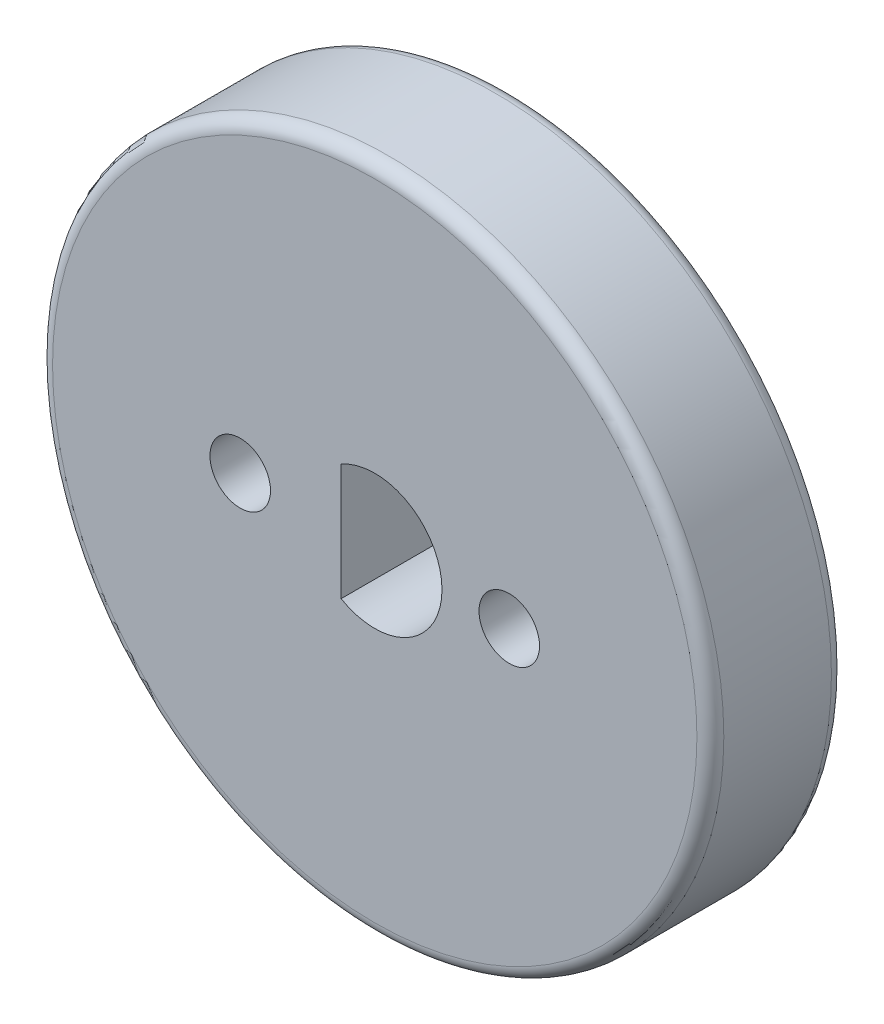
SolidWorks part; units mm, degrees
ref_plane "Front Plane" through (0, 0, 0) normal (0, 0, 1) x (1, 0, 0)
ref_plane "Top Plane" through (0, 0, 0) normal (0, 1, 0) x (1, 0, 0)
ref_plane "Right Plane" through (0, 0, 0) normal (1, 0, 0) x (0, 0, -1)
sketch "Sketch1" plane through (0, 0, 0) normal (0, 0, 1) x (1, 0, 0)
  line L0 (0, 0) -> (-2.5, -4.3301) construction
  line L1 (-2.5, -4.3301) -> (-2.5, 4.3301)
  line L2 (-2.5, 4.3301) -> (0, 0) construction
  line L3 (-5, 0) -> (0, 0) construction
  circle A0 centre (0, 0) radius 24.95
  circle A1 centre (0, 0) radius 15 construction
  circle A2 centre (0, 15) radius 2.25
  circle A3 centre (12.9904, -7.5) radius 2.25
  circle A4 centre (-12.9904, -7.5) radius 2.25
  arc A5 (-2.5, -4.3301) -> (-2.5, 4.3301) centre (0, 0) ccw
  point P13 (0, 0)
  dimension "D1" = 49.9
  dimension "D2" = 30
  dimension "D3" = 4.5
  dimension "D5" = 10
  dimension "D6" = 60
  dimension "D4" = 3
extrude "Boss-Extrude1" add sketch "Sketch1" along normal blind 6
sketch "Sketch2" plane through (0, 0, 6) normal (0, 0, 1) x (1, 0, 0)
  circle A0 centre (0, 0) radius 24.95
extrude "Boss-Extrude2" add sketch "Sketch2" along normal blind 4
sketch "Sketch3" plane through (0, 0, 6) normal (0, 0, -1) x (-1, 0, 0)
  line L0 (2.5, 4.3301) -> (2.5, -4.3301) construction
  line L1 (2.5, 4.3301) -> (2.5, -4.3301)
  arc A0 (2.5, 4.3301) -> (2.5, -4.3301) centre (0, 0) ccw construction
  arc A1 (2.5, 4.3301) -> (2.5, -4.3301) centre (0, 0) ccw
extrude "Cut-Extrude1" cut sketch "Sketch3" against normal through all
sketch "Sketch4" plane through (0, 0, 10) normal (0, 0, 1) x (1, 0, 0)
  line L0 (-24.95, 0) -> (24.95, 0) construction
  circle A0 centre (-10, 0) radius 2.25
  circle A1 centre (10, 0) radius 2.25
  circle A2 centre (0, 0) radius 24.95 construction
  point P6 (0, 0)
  point P8 (10.2194, 0)
  point P9 (0, 0)
  point P10 (24.95, 0)
  point P15 (11.4617, 5.7709)
  dimension "D3" = 4.5
  dimension "D4" = 4.5
  dimension "D1" = 10
  dimension "D2" = 10
extrude "Cut-Extrude2" cut sketch "Sketch4" against normal blind 6
fillet "Fillet1" radius 1 2 edges at (24.95, 0, 10) (24.95, 0, 0)
equation "\"`6\"=3"
